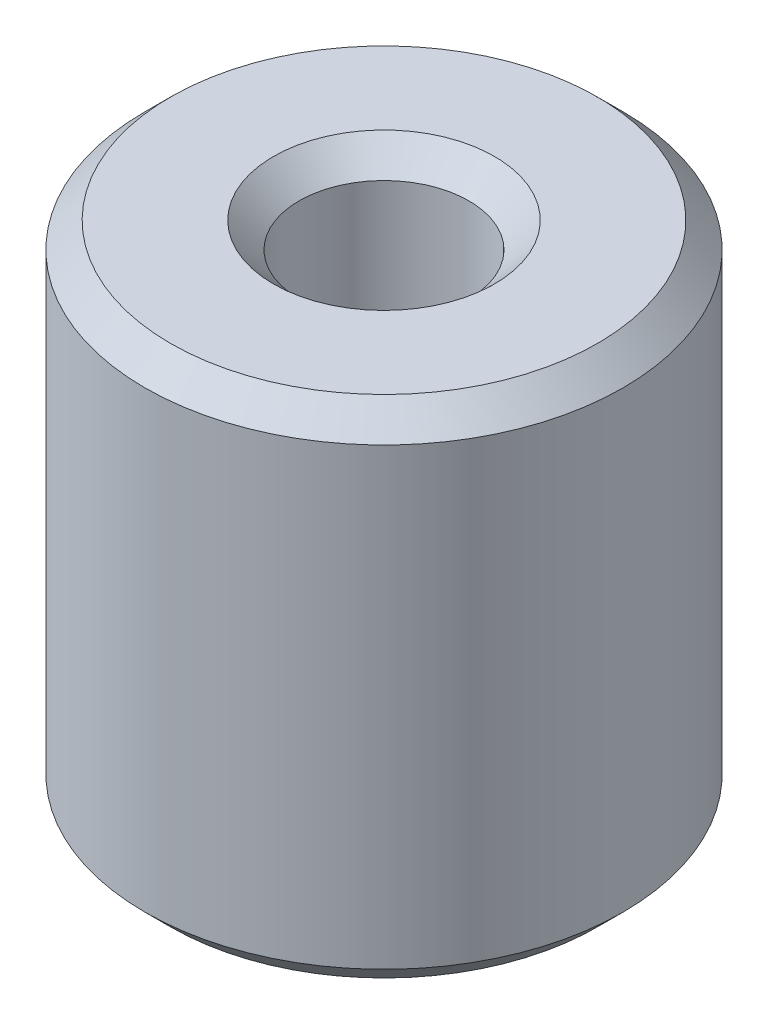
SolidWorks part; units mm, degrees
ref_plane "Front Plane" through (0, 0, 0) normal (0, 0, 1) x (1, 0, 0)
ref_plane "Top Plane" through (0, 0, 0) normal (0, 1, 0) x (1, 0, 0)
ref_plane "Right Plane" through (0, 0, 0) normal (1, 0, 0) x (0, 0, -1)
sketch "Sketch1" plane through (0, 0, 0) normal (0, 1, 0) x (1, 0, 0)
  circle A0 centre (0, 0) radius 5
  dimension "SLEEVE_OD" = 10
extrude "Boss-Extrude1" add sketch "Sketch1" along normal blind 10.5675
sketch "Sketch2" plane through (0, 0, 0) normal (0, 1, 0) x (1, 0, 0)
  circle A0 centre (0, 0) radius 1.7753
  dimension "BORE_D" = 3.5506
extrude "Cut-Extrude1" cut sketch "Sketch2" along normal through all
chamfer "Chamfer1" distance 0.5359 angle 45 4 edges at (0, 10.5675, 1.7753) (0, 0, 1.7753) (0, 0, 5) (0, 10.5675, 5)
